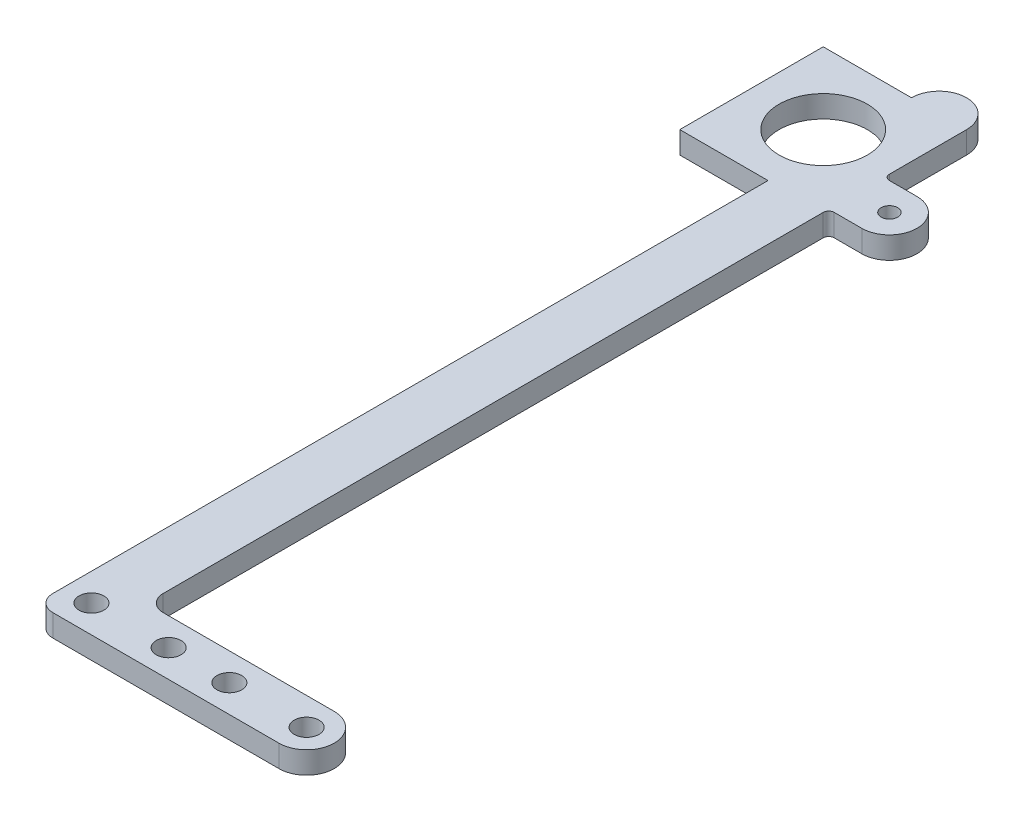
SolidWorks part; units mm, degrees
ref_plane "Front" through (0, 0, 0) normal (0, 0, 1) x (1, 0, 0)
ref_plane "Top" through (0, 0, 0) normal (0, 1, 0) x (1, 0, 0)
ref_plane "Right" through (0, 0, 0) normal (1, 0, 0) x (0, 0, -1)
sketch "Sketch1" plane through (0, 0, 0) normal (0, 1, 0) x (1, 0, 0)
  line L0 (0, 148.65) -> (0, 0)
  line L1 (10, 0) -> (10, 148.65)
  line L2 (0, 0) -> (10, 0)
  line L3 (0, 148.65) -> (10, 148.65) construction
  line L4 (5, 80) -> (68.8779, 80) construction
  arc A0 (0, 148.65) -> (10, 148.65) centre (5, 148.65) cw
  point P6 (25, 139.7)
  dimension "D1" = 10
  dimension "D4" = 148.65
  dimension "D3" = 20
extrude "Boss-Extrude1" add sketch "Sketch1" along normal blind 4 contours L3 L0 L2 L1 | A0 L3 region at (5, 0, -76.2926)
sketch "Sketch2" plane through (0, 4, 0) normal (0, 1, 0) x (1, 0, 0)
  line L0 (10, 0) -> (44, 0)
  line L1 (44, -10) -> (0, -10)
  line L2 (0, -10) -> (0, 0)
  line L3 (44, 0) -> (44, -10) construction
  line L4 (44, -5) -> (0, -5) construction
  arc A0 (44, 0) -> (44, -10) centre (44, -5) cw
  circle A1 centre (5, -5) radius 2.25
  circle A2 centre (19, -5) radius 2.25
  circle A3 centre (30, -5) radius 2.25
  circle A4 centre (44, -5) radius 2.25
  line M6 (0, 0) -> (10, 0)
  dimension "D3" = 4.5
  dimension "D4" = 4.5
  dimension "D5" = 4.5
  dimension "D6" = 4.5
  dimension "D1" = 10
  dimension "D2" = 44
  dimension "D7" = 14
  dimension "D8" = 14
  dimension "D9" = 5
extrude "Boss-Extrude2" add sketch "Sketch2" against normal blind 4 contours A0 L0 L2 L1 A4 A3 A2 A1 M6 region at (23.8964, 4, 5)
fillet "Fillet1" radius 3 2 edges at (10, 2, 0) (0, 2, 10)
sketch "Sketch3" [suppressed] plane through (0, 4, 0) normal (0, 1, 0) x (1, 0, 0)
  line L0 (0, -60) -> (-49, -60)
  line L1 (-49, -70) -> (10, -70)
  line L2 (10, 0) -> (10, -70)
  line L4 (-49, -60) -> (-49, -70) construction
  line L5 (-49, -65) -> (10, -65) construction
  line L6 (0, 148.65) -> (0, 0) construction
  line L7 (0, 0.3085) -> (0, -60)
  line L8 (0, 0) -> (10, 0) construction
  arc A0 (-49, -70) -> (-49, -60) centre (-49, -65) cw
  circle A1 centre (-49, -65) radius 2.25
  circle A2 centre (-35, -65) radius 2.25
  circle A3 centre (-9, -65) radius 2.25
  circle A4 centre (5, -65) radius 2.25
  dimension "D3" = 4.5
  dimension "D4" = 4.5
  dimension "D5" = 4.5
  dimension "D1" = 10
  dimension "D7" = 14
  dimension "D2" = 4.5
  dimension "D6" = 14
  dimension "D9" = 49
  dimension "D8" = 60
  dimension "D10" = 5
extrude "Boss-Extrude3" [suppressed] add sketch "Sketch3" against normal blind 4
fillet "Fillet2" [suppressed] radius 3
sketch "Sketch5" plane through (0, 4, 0) normal (0, 1, 0) x (1, 0, 0)
  line L3 (10, 3) -> (10, 148.65) construction
  line L5 (16, 133.65) -> (10, 133.65)
  line L7 (16, 123.65) -> (10, 123.65)
  arc A0 (16, 133.65) -> (16, 123.65) centre (16, 128.65) cw
  circle A1 centre (16, 128.65) radius 1.5
  arc A3 (10, 148.65) -> (0, 148.65) centre (5, 148.65) ccw construction
  line M7 (10, 3) -> (10, 148.65)
  dimension "D1" = 3
  dimension "D2" = 6
  dimension "D4" = 20
  dimension "D3" = 10
extrude "Boss-Extrude4" add sketch "Sketch5" against normal blind 4 contours A0 L5 L7 A1 M7 region at (20.8513, 4, -128.65)
fillet "Fillet3" radius 1 2 edges at (10, 2, -123.65) (10, 2, -133.65)
sketch "Sketch6" [suppressed] plane through (0, 4, 0) normal (0, 1, 0) x (1, 0, 0)
  line L0 (-6, 148.65) -> (0, 148.65)
  line L1 (0, 138.65) -> (-6, 138.65)
  line L2 (-6, 118.65) -> (0, 118.65)
  line L3 (0, 108.65) -> (-6, 108.65)
  line L4 (0, 148.65) -> (0, 0) construction
  line L5 (-3, 138.65) -> (-3, 118.65) construction
  line L9 (-6, 148.65) -> (-6, 138.65) construction
  line L10 (-6, 118.65) -> (-6, 108.65) construction
  arc A0 (-6, 148.65) -> (-6, 138.65) centre (-6, 143.65) ccw
  arc A1 (-6, 118.65) -> (-6, 108.65) centre (-6, 113.65) ccw
  circle A2 centre (-6, 143.65) radius 1.5
  circle A3 centre (-6, 113.65) radius 1.5
  arc A4 (10, 148.65) -> (0, 148.65) centre (5, 148.65) ccw construction
  point P14 (-3, 128.65)
  line M8 (0, 148.65) -> (0, -57)
  dimension "D1" = 10
  dimension "D5" = 3
  dimension "D6" = 3
  dimension "D2" = 10
  dimension "D3" = 30
  dimension "D4" = 6
  dimension "D7" = 20
extrude "Boss-Extrude5" [suppressed] add sketch "Sketch6" against normal blind 4 contours L0 A0 L1 A2 M8 | L2 A1 L3 A3 M8
fillet "Fillet4" [suppressed] radius 1
sketch "Sketch7" plane through (0, 4, 0) normal (0, 1, 0) x (1, 0, 0)
  line L1 (0, 148.65) -> (-16, 148.65)
  line L2 (0, 148.65) -> (0, 122.65)
  line L3 (0, 122.65) -> (-16, 122.65)
  line L4 (-16, 148.65) -> (-16, 122.65)
  point P8 (-16, 135.65)
  dimension "D1" = 16
  dimension "D3" = 26
extrude "Boss-Extrude6" add sketch "Sketch7" against normal blind 4
sketch "Sketch8" plane through (0, 4, 0) normal (0, 1, 0) x (1, 0, 0)
  line L0 (-16, 148.65) -> (-16, 122.65) construction
  line L1 (-16, 135.65) -> (10, 135.65) construction
  line L3 (10, 134.65) -> (10, 148.65) construction
  circle A0 centre (-3, 135.65) radius 8
  point P4 (-16, 135.65)
  dimension "D1" = 16
extrude "Cut-Extrude1" cut sketch "Sketch8" against normal blind 4
equation "\"D4@Sketch2\"=\"D3@Sketch2\""
equation "\"D5@Sketch2\"=\"D3@Sketch2\""
equation "\"D6@Sketch2\"=\"D3@Sketch2\""
equation "\"D9@Sketch2\"=(\"D1@Sketch2\"-\"D6@Sketch2\")/2+(\"D6@Sketch2\"/2)"
equation "\"D5@Sketch3\"=\"D2@Sketch3\""
equation "\"D4@Sketch3\"=\"D2@Sketch3\""
equation "\"D3@Sketch3\"=\"D2@Sketch3\""
equation "\"D7@Sketch3\"=\"D6@Sketch3\""
equation "\"D10@Sketch3\"=(\"D1@Sketch3\"-\"D2@Sketch3\")/2+\"D2@Sketch3\"/2"
equation "\"D2@Sketch6\"=\"D1@Sketch6\""
equation "\"D6@Sketch6\"=\"D5@Sketch6\""
